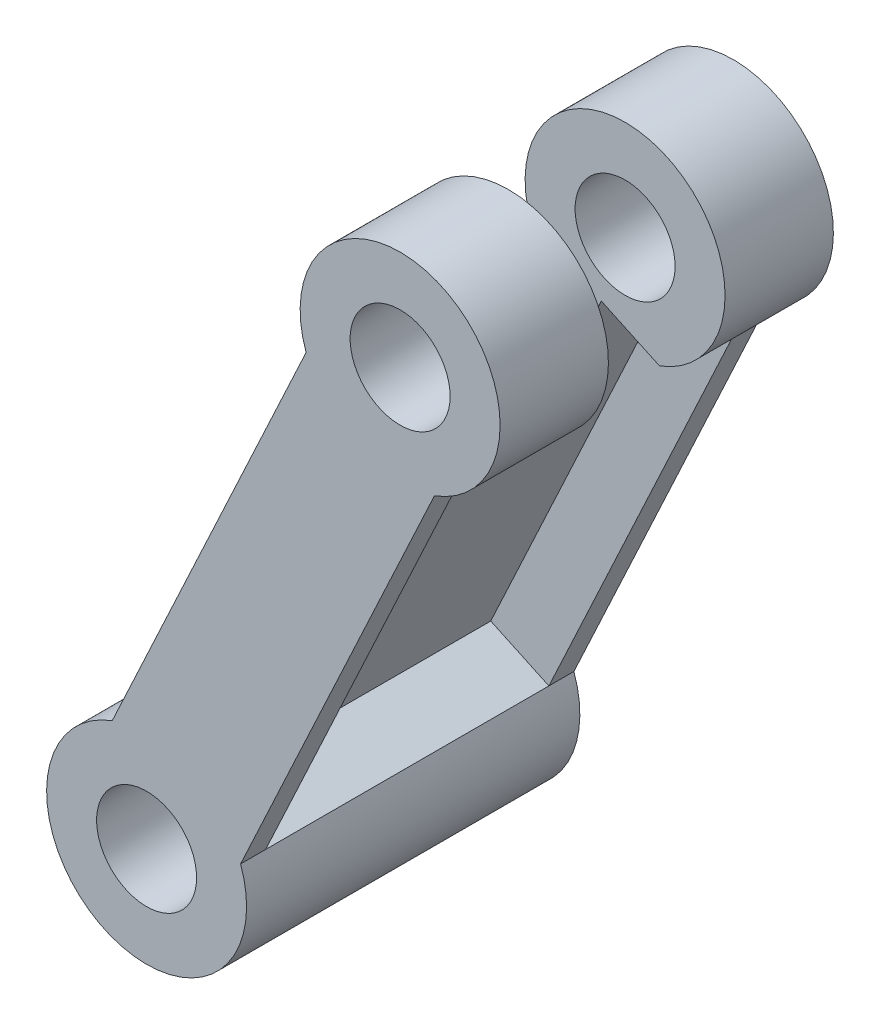
SolidWorks part; units mm, degrees
note: '?' marks a value the reader was unsure of.
material "1023 Carbon Steel Sheet (SS)"
ref_plane "Piano frontale" through (0, 0, 0) normal (0, 0, 1) x (1, 0, 0)
ref_plane "Piano superiore" through (0, 0, 0) normal (0, 1, 0) x (1, 0, 0)
ref_plane "Piano destro" through (0, 0, 0) normal (1, 0, 0) x (0, 0, -1)
sketch "Sketch1" plane through (0, 0, 0) normal (0, 0, 1) x (1, 0, 0)
  line L0 (0, 0) -> (152.1426, 326.2708) construction
  line L1 (0, 0) -> (129.1028, 0) construction
  line L2 (95.7255, 305.8475) -> (-20.6191, 56.3458)
  line L3 (172.7616, 269.925) -> (56.4171, 20.4233)
  circle A0 centre (0, 0) radius 60
  circle A1 centre (152.1426, 326.2708) radius 60
  dimension "D1" = 120
  dimension "D2" = 120
  dimension "D3" = 65
  dimension "D4" = 360
  dimension "D5" = 42.5
extrude "Boss-Extrude1" add sketch "Sketch1" along normal mid plane 200 contours A1 L2 A0 L3 | A1 | A0
sketch "Sketch2" plane through (0, 0, 0) normal (0, 0, 1) x (1, 0, 0)
  circle A0 centre (0, 0) radius 30
  circle A1 centre (152.1426, 326.2708) radius 30
  dimension "D1" = 60
  dimension "D2" = 60
extrude "Cut-Extrude1" cut sketch "Sketch2" against normal through all and the other way through all
ref_plane "Plane1" through (0, 0, 120) normal (0, 0, 1) x (1, 0, 0)
ref_axis "Axis1" through (199.0232, 426.8067, 0) along (-0.4226, -0.9063, 0)?
ref_plane "Plane2" through (0, 0, 0) normal (-0.9063, 0.4226, 0) x (0, 0, 1)
sketch "Sketch9" plane through (0, 0, 0) normal (0, 0, 1) x (1, 0, 0)
  circle A0 centre (152.1426, 326.2708) radius 60
  dimension "D1" = 120
extrude "Cut-Extrude4" cut sketch "Sketch9" against normal mid plane 70
sketch "Sketch10" plane through (-38.5181, 17.9613, 0) normal (-0.9063, 0.4226, 0) x (0, 0, 1)
  line L0 (-35, 317.6473) -> (-35, 272.6473)
  line L1 (-25, 262.6473) -> (0, 262.6473)
  line L2 (35, 317.6473) -> (35, 272.6473)
  line L3 (25, 262.6473) -> (0, 262.6473)
  line L4 (-35, 317.6473) -> (35, 317.6473)
  arc A0 (35, 272.6473) -> (25, 262.6473) centre (25, 272.6473) cw
  arc A1 (-35, 272.6473) -> (-25, 262.6473) centre (-25, 272.6473) ccw
  point P9 (35, 262.6473)
  dimension "D2" = 10
  dimension "D1" = 55
extrude "Cut-Extrude5" cut sketch "Sketch10" against normal through all
sketch "Sketch12" plane through (-38.5181, 17.9613, 0) normal (-0.9063, 0.4226, 0) x (0, 0, 1)
  line L0 (-85, 317.6473) -> (85, 317.6473)
  line L1 (-35, 317.6473) -> (-100, 317.6473) construction
  line L2 (100, 317.6473) -> (35, 317.6473) construction
  line L3 (85, 317.6473) -> (85, 42.3527)
  line L4 (100, 42.3527) -> (-100, 42.3527) construction
  line L5 (85, 42.3527) -> (-85, 42.3527)
  line L6 (-85, 42.3527) -> (-85, 317.6473)
  line L7 (-100, 317.6473) -> (-100, 42.3527) construction
  line L8 (100, 317.6473) -> (100, 42.3527) construction
  dimension "D1" = 15
  dimension "D2" = 15
extrude "Cut-Extrude6" cut sketch "Sketch12" against normal blind 38.5
mirror "Mirror1" about plane through (0, 0, 0) normal (-0.9063, 0.4226, 0) of "Cut-Extrude6"
